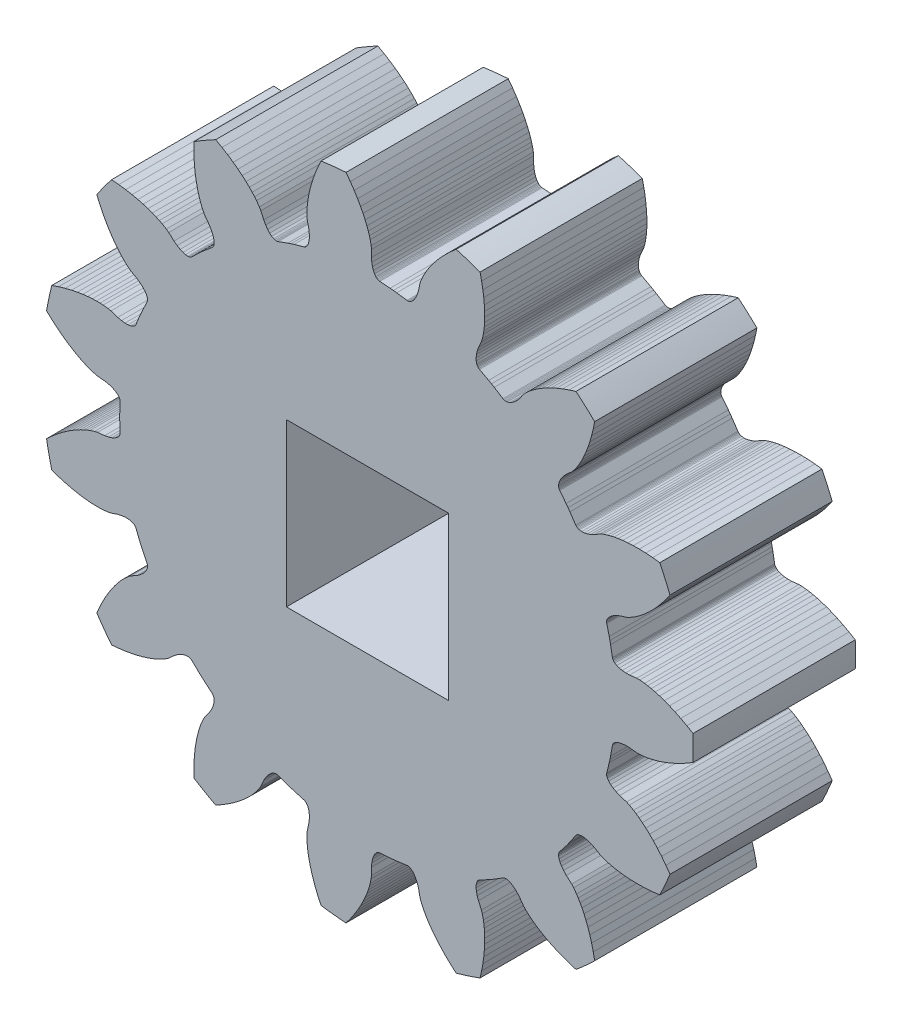
SolidWorks part; units mm, degrees
ref_plane "Front Plane" through (0, 0, 0) normal (0, 0, 1) x (1, 0, 0)
ref_plane "Top Plane" through (0, 0, 0) normal (0, 1, 0) x (1, 0, 0)
ref_plane "Right Plane" through (0, 0, 0) normal (1, 0, 0) x (0, 0, -1)
sketch "Model" plane through (0, 0, 0) normal (0, 0, 1) x (1, 0, 0)
  line L0 (11.6767, 4.5035) -> (11.5103, 4.2885)
  line L1 (11.5103, 4.2885) -> (11.3474, 4.0954)
  line L2 (11.3474, 4.0954) -> (11.1891, 3.9228)
  line L3 (11.1891, 3.9228) -> (11.0382, 3.7715)
  line L4 (11.0382, 3.7715) -> (10.8925, 3.6371)
  line L5 (10.8925, 3.6371) -> (10.7549, 3.5206)
  line L6 (10.7549, 3.5206) -> (10.6294, 3.4231)
  line L7 (10.6294, 3.4231) -> (10.5151, 3.3416)
  line L8 (10.5151, 3.3416) -> (10.4119, 3.2743)
  line L9 (10.4119, 3.2743) -> (10.2465, 3.1803)
  line L10 (10.2465, 3.1803) -> (10.1399, 3.1309)
  line L11 (10.1399, 3.1309) -> (9.873, 3.0467)
  line L12 (9.873, 3.0467) -> (9.7318, 2.9862)
  line L13 (9.7318, 2.9862) -> (9.613, 2.9201)
  line L14 (9.613, 2.9201) -> (9.5168, 2.8501)
  line L15 (9.5168, 2.8501) -> (9.4433, 2.778)
  line L16 (9.4433, 2.778) -> (9.3924, 2.7056)
  line L17 (9.3924, 2.7056) -> (9.3754, 2.6698)
  line L18 (9.3754, 2.6698) -> (9.364, 2.6346)
  line L19 (9.364, 2.6346) -> (9.3582, 2.6002)
  line L20 (9.3582, 2.6002) -> (9.3579, 2.5668)
  line L21 (9.3579, 2.5668) -> (9.363, 2.5346)
  line L22 (9.363, 2.5346) -> (9.4607, 2.1415)
  line L23 (9.4607, 2.1415) -> (9.488, 2.0167)
  line L24 (9.488, 2.0167) -> (9.5138, 1.8917)
  line L25 (9.5138, 1.8917) -> (9.5845, 1.4928)
  line L26 (9.5845, 1.4928) -> (9.5928, 1.4613)
  line L27 (9.5928, 1.4613) -> (9.6067, 1.4309)
  line L28 (9.6067, 1.4309) -> (9.626, 1.4019)
  line L29 (9.626, 1.4019) -> (9.6508, 1.3743)
  line L30 (9.6508, 1.3743) -> (9.6808, 1.3485)
  line L31 (9.6808, 1.3485) -> (9.7568, 1.3031)
  line L32 (9.7568, 1.3031) -> (9.8533, 1.2671)
  line L33 (9.8533, 1.2671) -> (9.9696, 1.2423)
  line L34 (9.9696, 1.2423) -> (10.105, 1.2303)
  line L35 (10.105, 1.2303) -> (10.2586, 1.2324)
  line L36 (10.2586, 1.2324) -> (10.5367, 1.2641)
  line L37 (10.5367, 1.2641) -> (10.6542, 1.2623)
  line L38 (10.6542, 1.2623) -> (10.8435, 1.2437)
  line L39 (10.8435, 1.2437) -> (10.9652, 1.2242)
  line L40 (10.9652, 1.2242) -> (11.1027, 1.1962)
  line L41 (11.1027, 1.1962) -> (11.2571, 1.1582)
  line L42 (11.2571, 1.1582) -> (11.4301, 1.1077)
  line L43 (11.4301, 1.1077) -> (11.6179, 1.0442)
  line L44 (11.6179, 1.0442) -> (11.8173, 0.9674)
  line L45 (11.8173, 0.9674) -> (12.0321, 0.8741)
  line L46 (12.0321, 0.8741) -> (12.2594, 0.764)
  line L47 (12.2594, 0.764) -> (12.499, 0.6352)
  line L48 (12.499, 0.6352) -> (12.7405, 0.492)
  line L49 (12.7405, -0.492) -> (12.499, -0.6352)
  line L50 (12.499, -0.6352) -> (12.2594, -0.764)
  line L51 (12.2594, -0.764) -> (12.0321, -0.8741)
  line L52 (12.0321, -0.8741) -> (11.8173, -0.9674)
  line L53 (11.8173, -0.9674) -> (11.6179, -1.0442)
  line L54 (11.6179, -1.0442) -> (11.4301, -1.1077)
  line L55 (11.4301, -1.1077) -> (11.2571, -1.1582)
  line L56 (11.2571, -1.1582) -> (11.1027, -1.1962)
  line L57 (11.1027, -1.1962) -> (10.9652, -1.2242)
  line L58 (10.9652, -1.2242) -> (10.8435, -1.2437)
  line L59 (10.8435, -1.2437) -> (10.6542, -1.2623)
  line L60 (10.6542, -1.2623) -> (10.5367, -1.2641)
  line L61 (10.5367, -1.2641) -> (10.2586, -1.2324)
  line L62 (10.2586, -1.2324) -> (10.105, -1.2303)
  line L63 (10.105, -1.2303) -> (9.9696, -1.2423)
  line L64 (9.9696, -1.2423) -> (9.8533, -1.2671)
  line L65 (9.8533, -1.2671) -> (9.7568, -1.3031)
  line L66 (9.7568, -1.3031) -> (9.6808, -1.3485)
  line L67 (9.6808, -1.3485) -> (9.6508, -1.3743)
  line L68 (9.6508, -1.3743) -> (9.626, -1.4019)
  line L69 (9.626, -1.4019) -> (9.6067, -1.4309)
  line L70 (9.6067, -1.4309) -> (9.5928, -1.4613)
  line L71 (9.5928, -1.4613) -> (9.5845, -1.4928)
  line L72 (9.5845, -1.4928) -> (9.5138, -1.8917)
  line L73 (9.5138, -1.8917) -> (9.488, -2.0167)
  line L74 (9.488, -2.0167) -> (9.4607, -2.1415)
  line L75 (9.4607, -2.1415) -> (9.363, -2.5346)
  line L76 (9.363, -2.5346) -> (9.3579, -2.5668)
  line L77 (9.3579, -2.5668) -> (9.3582, -2.6002)
  line L78 (9.3582, -2.6002) -> (9.364, -2.6346)
  line L79 (9.364, -2.6346) -> (9.3754, -2.6698)
  line L80 (9.3754, -2.6698) -> (9.3924, -2.7056)
  line L81 (9.3924, -2.7056) -> (9.4433, -2.778)
  line L82 (9.4433, -2.778) -> (9.5168, -2.8501)
  line L83 (9.5168, -2.8501) -> (9.613, -2.9201)
  line L84 (9.613, -2.9201) -> (9.7318, -2.9862)
  line L85 (9.7318, -2.9862) -> (9.873, -3.0467)
  line L86 (9.873, -3.0467) -> (10.1399, -3.1309)
  line L87 (10.1399, -3.1309) -> (10.2465, -3.1803)
  line L88 (10.2465, -3.1803) -> (10.4119, -3.2743)
  line L89 (10.4119, -3.2743) -> (10.5151, -3.3416)
  line L90 (10.5151, -3.3416) -> (10.6294, -3.4231)
  line L91 (10.6294, -3.4231) -> (10.7549, -3.5206)
  line L92 (10.7549, -3.5206) -> (10.8925, -3.6371)
  line L93 (10.8925, -3.6371) -> (11.0382, -3.7715)
  line L94 (11.0382, -3.7715) -> (11.1891, -3.9228)
  line L95 (11.1891, -3.9228) -> (11.3474, -4.0954)
  line L96 (11.3474, -4.0954) -> (11.5103, -4.2885)
  line L97 (11.5103, -4.2885) -> (11.6767, -4.5035)
  line L98 (11.6767, -4.5035) -> (11.8391, -4.7326)
  line L99 (11.4389, -5.6315) -> (11.16, -5.6641)
  line L100 (11.16, -5.6641) -> (10.8888, -5.6843)
  line L101 (10.8888, -5.6843) -> (10.6364, -5.6925)
  line L102 (10.6364, -5.6925) -> (10.4021, -5.6903)
  line L103 (10.4021, -5.6903) -> (10.1888, -5.6793)
  line L104 (10.1888, -5.6793) -> (9.9914, -5.661)
  line L105 (9.9914, -5.661) -> (9.8128, -5.6367)
  line L106 (9.8128, -5.6367) -> (9.6563, -5.6087)
  line L107 (9.6563, -5.6087) -> (9.5193, -5.5783)
  line L108 (9.5193, -5.5783) -> (9.4002, -5.5466)
  line L109 (9.4002, -5.5466) -> (9.2197, -5.4866)
  line L110 (9.2197, -5.4866) -> (9.1116, -5.4405)
  line L111 (9.1116, -5.4405) -> (8.8704, -5.2984)
  line L112 (8.8704, -5.2984) -> (8.731, -5.234)
  line L113 (8.731, -5.234) -> (8.6024, -5.1899)
  line L114 (8.6024, -5.1899) -> (8.486, -5.1653)
  line L115 (8.486, -5.1653) -> (8.3833, -5.1589)
  line L116 (8.3833, -5.1589) -> (8.2954, -5.1695)
  line L117 (8.2954, -5.1695) -> (8.2574, -5.1808)
  line L118 (8.2574, -5.1808) -> (8.2236, -5.1959)
  line L119 (8.2236, -5.1959) -> (8.1941, -5.2146)
  line L120 (8.1941, -5.2146) -> (8.1691, -5.2367)
  line L121 (8.1691, -5.2367) -> (8.1487, -5.2621)
  line L122 (8.1487, -5.2621) -> (7.9219, -5.5977)
  line L123 (7.9219, -5.5977) -> (7.8475, -5.7015)
  line L124 (7.8475, -5.7015) -> (7.7717, -5.8044)
  line L125 (7.7717, -5.8044) -> (7.5226, -6.1238)
  line L126 (7.5226, -6.1238) -> (7.5048, -6.151)
  line L127 (7.5048, -6.151) -> (7.4915, -6.1817)
  line L128 (7.4915, -6.1817) -> (7.4828, -6.2155)
  line L129 (7.4828, -6.2155) -> (7.4789, -6.2523)
  line L130 (7.4789, -6.2523) -> (7.4799, -6.2919)
  line L131 (7.4799, -6.2919) -> (7.4969, -6.3788)
  line L132 (7.4969, -6.3788) -> (7.5348, -6.4746)
  line L133 (7.5348, -6.4746) -> (7.5942, -6.5776)
  line L134 (7.5942, -6.5776) -> (7.6759, -6.6863)
  line L135 (7.6759, -6.6863) -> (7.7802, -6.799)
  line L136 (7.7802, -6.799) -> (7.9899, -6.9845)
  line L137 (7.9899, -6.9845) -> (8.0671, -7.073)
  line L138 (8.0671, -7.073) -> (8.1799, -7.2261)
  line L139 (8.1799, -7.2261) -> (8.2469, -7.3296)
  line L140 (8.2469, -7.3296) -> (8.3182, -7.4505)
  line L141 (8.3182, -7.4505) -> (8.3931, -7.5907)
  line L142 (8.3931, -7.5907) -> (8.4714, -7.753)
  line L143 (8.4714, -7.753) -> (8.5499, -7.9351)
  line L144 (8.5499, -7.9351) -> (8.6262, -8.1346)
  line L145 (8.6262, -8.1346) -> (8.7007, -8.3567)
  line L146 (8.7007, -8.3567) -> (8.7709, -8.5993)
  line L147 (8.7709, -8.5993) -> (8.8355, -8.8635)
  line L148 (8.8355, -8.8635) -> (8.8906, -9.1388)
  line L149 (8.1594, -9.7972) -> (7.8914, -9.7136)
  line L150 (7.8914, -9.7136) -> (7.6354, -9.6217)
  line L151 (7.6354, -9.6217) -> (7.4015, -9.5265)
  line L152 (7.4015, -9.5265) -> (7.1884, -9.4292)
  line L153 (7.1884, -9.4292) -> (6.9979, -9.3325)
  line L154 (6.9979, -9.3325) -> (6.8251, -9.2354)
  line L155 (6.8251, -9.2354) -> (6.6718, -9.1406)
  line L156 (6.6718, -9.1406) -> (6.5402, -9.0514)
  line L157 (6.5402, -9.0514) -> (6.4274, -8.9679)
  line L158 (6.4274, -8.9679) -> (6.3315, -8.8905)
  line L159 (6.3315, -8.8905) -> (6.191, -8.7623)
  line L160 (6.191, -8.7623) -> (6.111, -8.6762)
  line L161 (6.111, -8.6762) -> (5.9485, -8.4483)
  line L162 (5.9485, -8.4483) -> (5.8473, -8.3327)
  line L163 (5.8473, -8.3327) -> (5.7478, -8.2402)
  line L164 (5.7478, -8.2402) -> (5.6515, -8.1703)
  line L165 (5.6515, -8.1703) -> (5.5602, -8.1226)
  line L166 (5.5602, -8.1226) -> (5.4756, -8.0966)
  line L167 (5.4756, -8.0966) -> (5.4363, -8.0915)
  line L168 (5.4363, -8.0915) -> (5.3993, -8.0916)
  line L169 (5.3993, -8.0916) -> (5.3647, -8.0966)
  line L170 (5.3647, -8.0966) -> (5.3329, -8.1067)
  line L171 (5.3329, -8.1067) -> (5.3039, -8.1215)
  line L172 (5.3039, -8.1215) -> (4.9602, -8.3359)
  line L173 (4.9602, -8.3359) -> (4.85, -8.4004)
  line L174 (4.85, -8.4004) -> (4.739, -8.4636)
  line L175 (4.739, -8.4636) -> (4.3815, -8.6541)
  line L176 (4.3815, -8.6541) -> (4.3542, -8.6717)
  line L177 (4.3542, -8.6717) -> (4.3295, -8.6943)
  line L178 (4.3295, -8.6943) -> (4.3078, -8.7217)
  line L179 (4.3078, -8.7217) -> (4.2893, -8.7537)
  line L180 (4.2893, -8.7537) -> (4.2741, -8.7903)
  line L181 (4.2741, -8.7903) -> (4.2543, -8.8766)
  line L182 (4.2543, -8.8766) -> (4.2499, -8.9795)
  line L183 (4.2499, -8.9795) -> (4.2623, -9.0978)
  line L184 (4.2623, -9.0978) -> (4.2927, -9.2303)
  line L185 (4.2927, -9.2303) -> (4.3422, -9.3757)
  line L186 (4.3422, -9.3757) -> (4.4583, -9.6304)
  line L187 (4.4583, -9.6304) -> (4.4928, -9.7427)
  line L188 (4.4928, -9.7427) -> (4.5336, -9.9285)
  line L189 (4.5336, -9.9285) -> (4.5527, -10.0502)
  line L190 (4.5527, -10.0502) -> (4.5686, -10.1897)
  line L191 (4.5686, -10.1897) -> (4.5801, -10.3482)
  line L192 (4.5801, -10.3482) -> (4.5856, -10.5284)
  line L193 (4.5856, -10.5284) -> (4.5832, -10.7266)
  line L194 (4.5832, -10.7266) -> (4.5718, -10.94)
  line L195 (4.5718, -10.94) -> (4.5495, -11.1731)
  line L196 (4.5495, -11.1731) -> (4.5149, -11.4233)
  line L197 (4.5149, -11.4233) -> (4.4665, -11.691)
  line L198 (4.4665, -11.691) -> (4.4049, -11.9649)
  line L199 (3.4691, -12.2689) -> (3.2583, -12.0835)
  line L200 (3.2583, -12.0835) -> (3.0618, -11.8955)
  line L201 (3.0618, -11.8955) -> (2.8868, -11.7134)
  line L202 (2.8868, -11.7134) -> (2.7317, -11.5378)
  line L203 (2.7317, -11.5378) -> (2.597, -11.3719)
  line L204 (2.597, -11.3719) -> (2.4786, -11.213)
  line L205 (2.4786, -11.213) -> (2.3771, -11.064)
  line L206 (2.3771, -11.064) -> (2.2932, -10.929)
  line L207 (2.2932, -10.929) -> (2.2242, -10.8068)
  line L208 (2.2242, -10.8068) -> (2.168, -10.6971)
  line L209 (2.168, -10.6971) -> (2.0918, -10.5228)
  line L210 (2.0918, -10.5228) -> (2.0538, -10.4117)
  line L211 (2.0538, -10.4117) -> (1.998, -10.1374)
  line L212 (1.998, -10.1374) -> (1.9526, -9.9906)
  line L213 (1.9526, -9.9906) -> (1.8993, -9.8656)
  line L214 (1.8993, -9.8656) -> (1.8397, -9.7626)
  line L215 (1.8397, -9.7626) -> (1.7757, -9.6819)
  line L216 (1.7757, -9.6819) -> (1.709, -9.6238)
  line L217 (1.709, -9.6238) -> (1.6752, -9.6031)
  line L218 (1.6752, -9.6031) -> (1.6414, -9.5881)
  line L219 (1.6414, -9.5881) -> (1.6077, -9.5787)
  line L220 (1.6077, -9.5787) -> (1.5745, -9.5749)
  line L221 (1.5745, -9.5749) -> (1.542, -9.5767)
  line L222 (1.542, -9.5767) -> (1.1409, -9.6327)
  line L223 (1.1409, -9.6327) -> (1.0139, -9.6469)
  line L224 (1.0139, -9.6469) -> (0.8868, -9.6594)
  line L225 (0.8868, -9.6594) -> (0.4828, -9.688)
  line L226 (0.4828, -9.688) -> (0.4506, -9.693)
  line L227 (0.4506, -9.693) -> (0.4189, -9.7036)
  line L228 (0.4189, -9.7036) -> (0.388, -9.7198)
  line L229 (0.388, -9.7198) -> (0.358, -9.7415)
  line L230 (0.358, -9.7415) -> (0.3292, -9.7688)
  line L231 (0.3292, -9.7688) -> (0.2761, -9.8396)
  line L232 (0.2761, -9.8396) -> (0.2302, -9.9318)
  line L233 (0.2302, -9.9318) -> (0.1934, -10.0449)
  line L234 (0.1934, -10.0449) -> (0.1672, -10.1783)
  line L235 (0.1672, -10.1783) -> (0.1534, -10.3312)
  line L236 (0.1534, -10.3312) -> (0.1558, -10.6111)
  line L237 (0.1558, -10.6111) -> (0.1417, -10.7278)
  line L238 (0.1417, -10.7278) -> (0.1034, -10.9141)
  line L239 (0.1034, -10.9141) -> (0.0713, -11.0331)
  line L240 (0.0713, -11.0331) -> (0.0291, -11.1669)
  line L241 (0.0291, -11.1669) -> (-0.0249, -11.3165)
  line L242 (-0.0249, -11.3165) -> (-0.0932, -11.4833)
  line L243 (-0.0932, -11.4833) -> (-0.1759, -11.6634)
  line L244 (-0.1759, -11.6634) -> (-0.2732, -11.8536)
  line L245 (-0.2732, -11.8536) -> (-0.3884, -12.0576)
  line L246 (-0.3884, -12.0576) -> (-0.5217, -12.2721)
  line L247 (-0.5217, -12.2721) -> (-0.6748, -12.4969)
  line L248 (-0.6748, -12.4969) -> (-0.8425, -12.7221)
  line L249 (-1.821, -12.6193) -> (-1.9382, -12.3641)
  line L250 (-1.9382, -12.3641) -> (-2.0412, -12.1124)
  line L251 (-2.0412, -12.1124) -> (-2.127, -11.8749)
  line L252 (-2.127, -11.8749) -> (-2.1973, -11.6514)
  line L253 (-2.1973, -11.6514) -> (-2.2529, -11.4451)
  line L254 (-2.2529, -11.4451) -> (-2.2964, -11.2517)
  line L255 (-2.2964, -11.2517) -> (-2.3285, -11.0743)
  line L256 (-2.3285, -11.0743) -> (-2.3502, -10.9169)
  line L257 (-2.3502, -10.9169) -> (-2.3637, -10.7771)
  line L258 (-2.3637, -10.7771) -> (-2.3703, -10.6541)
  line L259 (-2.3703, -10.6541) -> (-2.369, -10.4639)
  line L260 (-2.369, -10.4639) -> (-2.3586, -10.3469)
  line L261 (-2.3586, -10.3469) -> (-2.298, -10.0736)
  line L262 (-2.298, -10.0736) -> (-2.2798, -9.9211)
  line L263 (-2.2798, -9.9211) -> (-2.2776, -9.7852)
  line L264 (-2.2776, -9.7852) -> (-2.2901, -9.6669)
  line L265 (-2.2901, -9.6669) -> (-2.3158, -9.5671)
  line L266 (-2.3158, -9.5671) -> (-2.3531, -9.4868)
  line L267 (-2.3531, -9.4868) -> (-2.3756, -9.4542)
  line L268 (-2.3756, -9.4542) -> (-2.4004, -9.4268)
  line L269 (-2.4004, -9.4268) -> (-2.4273, -9.4045)
  line L270 (-2.4273, -9.4045) -> (-2.456, -9.3875)
  line L271 (-2.456, -9.3875) -> (-2.4865, -9.3759)
  line L272 (-2.4865, -9.3759) -> (-2.8758, -9.2639)
  line L273 (-2.8758, -9.2639) -> (-2.9975, -9.2252)
  line L274 (-2.9975, -9.2252) -> (-3.1187, -9.185)
  line L275 (-3.1187, -9.185) -> (-3.4994, -9.0468)
  line L276 (-3.4994, -9.0468) -> (-3.5309, -9.0383)
  line L277 (-3.5309, -9.0383) -> (-3.5641, -9.0351)
  line L278 (-3.5641, -9.0351) -> (-3.599, -9.0373)
  line L279 (-3.599, -9.0373) -> (-3.6352, -9.045)
  line L280 (-3.6352, -9.045) -> (-3.6725, -9.0581)
  line L281 (-3.6725, -9.0581) -> (-3.7499, -9.1012)
  line L282 (-3.7499, -9.1012) -> (-3.8293, -9.1668)
  line L283 (-3.8293, -9.1668) -> (-3.9089, -9.2551)
  line L284 (-3.9089, -9.2551) -> (-3.9871, -9.3664)
  line L285 (-3.9871, -9.3664) -> (-4.062, -9.5004)
  line L286 (-4.062, -9.5004) -> (-4.1736, -9.7571)
  line L287 (-4.1736, -9.7571) -> (-4.234, -9.858)
  line L288 (-4.234, -9.858) -> (-4.3447, -10.0126)
  line L289 (-4.3447, -10.0126) -> (-4.4224, -10.1082)
  line L290 (-4.4224, -10.1082) -> (-4.5154, -10.2134)
  line L291 (-4.5154, -10.2134) -> (-4.6255, -10.328)
  line L292 (-4.6255, -10.328) -> (-4.7558, -10.4526)
  line L293 (-4.7558, -10.4526) -> (-4.9046, -10.5835)
  line L294 (-4.9046, -10.5835) -> (-5.0709, -10.7177)
  line L295 (-5.0709, -10.7177) -> (-5.2591, -10.8572)
  line L296 (-5.2591, -10.8572) -> (-5.4681, -10.999)
  line L297 (-5.4681, -10.999) -> (-5.6994, -11.142)
  line L298 (-5.6994, -11.142) -> (-5.9442, -11.2796)
  line L299 (-6.7963, -10.7876) -> (-6.7996, -10.5068)
  line L300 (-6.7996, -10.5068) -> (-6.7913, -10.235)
  line L301 (-6.7913, -10.235) -> (-6.7731, -9.9831)
  line L302 (-6.7731, -9.9831) -> (-6.7464, -9.7504)
  line L303 (-6.7464, -9.7504) -> (-6.7132, -9.5393)
  line L304 (-6.7132, -9.5393) -> (-6.6743, -9.3449)
  line L305 (-6.6743, -9.3449) -> (-6.6315, -9.1698)
  line L306 (-6.6315, -9.1698) -> (-6.5873, -9.0171)
  line L307 (-6.5873, -9.0171) -> (-6.5428, -8.884)
  line L308 (-6.5428, -8.884) -> (-6.4988, -8.7689)
  line L309 (-6.4988, -8.7689) -> (-6.4203, -8.5957)
  line L310 (-6.4203, -8.5957) -> (-6.3631, -8.493)
  line L311 (-6.3631, -8.493) -> (-6.1966, -8.268)
  line L312 (-6.1966, -8.268) -> (-6.118, -8.1361)
  line L313 (-6.118, -8.1361) -> (-6.0607, -8.0128)
  line L314 (-6.0607, -8.0128) -> (-6.024, -7.8996)
  line L315 (-6.024, -7.8996) -> (-6.0069, -7.7981)
  line L316 (-6.0069, -7.7981) -> (-6.0083, -7.7096)
  line L317 (-6.0083, -7.7096) -> (-6.0156, -7.6706)
  line L318 (-6.0156, -7.6706) -> (-6.0271, -7.6354)
  line L319 (-6.0271, -7.6354) -> (-6.0426, -7.6042)
  line L320 (-6.0426, -7.6042) -> (-6.062, -7.577)
  line L321 (-6.062, -7.577) -> (-6.0851, -7.554)
  line L322 (-6.0851, -7.554) -> (-6.3951, -7.2934)
  line L323 (-6.3951, -7.2934) -> (-6.4906, -7.2085)
  line L324 (-6.4906, -7.2085) -> (-6.5849, -7.1224)
  line L325 (-6.5849, -7.1224) -> (-6.8765, -6.8413)
  line L326 (-6.8765, -6.8413) -> (-6.9018, -6.8208)
  line L327 (-6.9018, -6.8208) -> (-6.9309, -6.8043)
  line L328 (-6.9309, -6.8043) -> (-6.9636, -6.7922)
  line L329 (-6.9636, -6.7922) -> (-6.9998, -6.7844)
  line L330 (-6.9998, -6.7844) -> (-7.0393, -6.7813)
  line L331 (-7.0393, -6.7813) -> (-7.1275, -6.7891)
  line L332 (-7.1275, -6.7891) -> (-7.2267, -6.8167)
  line L333 (-7.2267, -6.8167) -> (-7.3354, -6.8651)
  line L334 (-7.3354, -6.8651) -> (-7.452, -6.9349)
  line L335 (-7.452, -6.9349) -> (-7.575, -7.0269)
  line L336 (-7.575, -7.0269) -> (-7.7814, -7.216)
  line L337 (-7.7814, -7.216) -> (-7.8775, -7.2836)
  line L338 (-7.8775, -7.2836) -> (-8.0416, -7.3798)
  line L339 (-8.0416, -7.3798) -> (-8.1515, -7.4356)
  line L340 (-8.1515, -7.4356) -> (-8.2792, -7.4938)
  line L341 (-8.2792, -7.4938) -> (-8.4264, -7.5537)
  line L342 (-8.4264, -7.5537) -> (-8.5961, -7.6146)
  line L343 (-8.5961, -7.6146) -> (-8.7853, -7.6736)
  line L344 (-8.7853, -7.6736) -> (-8.9918, -7.7286)
  line L345 (-8.9918, -7.7286) -> (-9.2204, -7.7795)
  line L346 (-9.2204, -7.7795) -> (-9.469, -7.824)
  line L347 (-9.469, -7.824) -> (-9.7385, -7.8606)
  line L348 (-9.7385, -7.8606) -> (-10.0181, -7.8867)
  line L349 (-10.5964, -7.0906) -> (-10.4852, -6.8328)
  line L350 (-10.4852, -6.8328) -> (-10.3671, -6.5879)
  line L351 (-10.3671, -6.5879) -> (-10.248, -6.3651)
  line L352 (-10.248, -6.3651) -> (-10.129, -6.1634)
  line L353 (-10.129, -6.1634) -> (-10.0128, -5.984)
  line L354 (-10.0128, -5.984) -> (-9.8982, -5.8223)
  line L355 (-9.8982, -5.8223) -> (-9.7879, -5.6798)
  line L356 (-9.7879, -5.6798) -> (-9.6854, -5.5582)
  line L357 (-9.6854, -5.5582) -> (-9.5906, -5.4548)
  line L358 (-9.5906, -5.4548) -> (-9.5036, -5.3675)
  line L359 (-9.5036, -5.3675) -> (-9.3614, -5.2412)
  line L360 (-9.3614, -5.2412) -> (-9.2674, -5.1707)
  line L361 (-9.2674, -5.1707) -> (-9.0238, -5.0328)
  line L362 (-9.0238, -5.0328) -> (-8.8983, -4.9443)
  line L363 (-8.8983, -4.9443) -> (-8.7958, -4.855)
  line L364 (-8.7958, -4.855) -> (-8.7163, -4.7665)
  line L365 (-8.7163, -4.7665) -> (-8.6593, -4.6807)
  line L366 (-8.6593, -4.6807) -> (-8.6246, -4.5993)
  line L367 (-8.6246, -4.5993) -> (-8.6154, -4.5607)
  line L368 (-8.6154, -4.5607) -> (-8.6116, -4.5239)
  line L369 (-8.6116, -4.5239) -> (-8.6131, -4.489)
  line L370 (-8.6131, -4.489) -> (-8.6197, -4.4563)
  line L371 (-8.6197, -4.4563) -> (-8.6315, -4.4259)
  line L372 (-8.6315, -4.4259) -> (-8.8087, -4.0617)
  line L373 (-8.8087, -4.0617) -> (-8.8614, -3.9453)
  line L374 (-8.8614, -3.9453) -> (-8.9126, -3.8283)
  line L375 (-8.9126, -3.8283) -> (-9.0646, -3.4529)
  line L376 (-9.0646, -3.4529) -> (-9.0794, -3.4239)
  line L377 (-9.0794, -3.4239) -> (-9.0993, -3.397)
  line L378 (-9.0993, -3.397) -> (-9.1242, -3.3726)
  line L379 (-9.1242, -3.3726) -> (-9.1541, -3.3508)
  line L380 (-9.1541, -3.3508) -> (-9.1889, -3.3318)
  line L381 (-9.1889, -3.3318) -> (-9.2727, -3.3032)
  line L382 (-9.2727, -3.3032) -> (-9.3745, -3.2881)
  line L383 (-9.3745, -3.2881) -> (-9.4935, -3.288)
  line L384 (-9.4935, -3.288) -> (-9.6284, -3.3043)
  line L385 (-9.6284, -3.3043) -> (-9.7782, -3.3384)
  line L386 (-9.7782, -3.3384) -> (-10.0437, -3.4272)
  line L387 (-10.0437, -3.4272) -> (-10.159, -3.4498)
  line L388 (-10.159, -3.4498) -> (-10.348, -3.471)
  line L389 (-10.348, -3.471) -> (-10.471, -3.4772)
  line L390 (-10.471, -3.4772) -> (-10.6114, -3.4785)
  line L391 (-10.6114, -3.4785) -> (-10.7703, -3.4733)
  line L392 (-10.7703, -3.4733) -> (-10.95, -3.4599)
  line L393 (-10.95, -3.4599) -> (-11.1469, -3.4369)
  line L394 (-11.1469, -3.4369) -> (-11.3579, -3.4032)
  line L395 (-11.3579, -3.4032) -> (-11.5875, -3.3566)
  line L396 (-11.5875, -3.3566) -> (-11.8327, -3.2961)
  line L397 (-11.8327, -3.2961) -> (-12.0938, -3.22)
  line L398 (-12.0938, -3.22) -> (-12.3598, -3.1301)
  line L399 (-12.5643, -2.1677) -> (-12.3579, -1.9774)
  line L400 (-12.3579, -1.9774) -> (-12.1504, -1.8016)
  line L401 (-12.1504, -1.8016) -> (-11.951, -1.6466)
  line L402 (-11.951, -1.6466) -> (-11.7602, -1.5107)
  line L403 (-11.7602, -1.5107) -> (-11.5811, -1.3941)
  line L404 (-11.5811, -1.3941) -> (-11.4106, -1.293)
  line L405 (-11.4106, -1.293) -> (-11.2519, -1.2076)
  line L406 (-11.2519, -1.2076) -> (-11.1088, -1.1383)
  line L407 (-11.1088, -1.1383) -> (-10.9801, -1.0823)
  line L408 (-10.9801, -1.0823) -> (-10.8651, -1.038)
  line L409 (-10.8651, -1.038) -> (-10.6838, -0.9805)
  line L410 (-10.6838, -0.9805) -> (-10.5693, -0.9542)
  line L411 (-10.5693, -0.9542) -> (-10.2907, -0.9274)
  line L412 (-10.2907, -0.9274) -> (-10.14, -0.8976)
  line L413 (-10.14, -0.8976) -> (-10.0101, -0.8576)
  line L414 (-10.0101, -0.8576) -> (-9.9014, -0.8092)
  line L415 (-9.9014, -0.8092) -> (-9.8145, -0.754)
  line L416 (-9.8145, -0.754) -> (-9.7497, -0.6937)
  line L417 (-9.7497, -0.6937) -> (-9.7256, -0.6622)
  line L418 (-9.7256, -0.6622) -> (-9.7071, -0.6301)
  line L419 (-9.7071, -0.6301) -> (-9.6943, -0.5977)
  line L420 (-9.6943, -0.5977) -> (-9.687, -0.5651)
  line L421 (-9.687, -0.5651) -> (-9.6854, -0.5325)
  line L422 (-9.6854, -0.5325) -> (-9.6992, -0.1277)
  line L423 (-9.6992, -0.1277) -> (-9.7, 0)
  line L424 (-9.7, 0) -> (-9.6992, 0.1277)
  line L425 (-9.6992, 0.1277) -> (-9.6854, 0.5325)
  line L426 (-9.6854, 0.5325) -> (-9.687, 0.5651)
  line L427 (-9.687, 0.5651) -> (-9.6943, 0.5977)
  line L428 (-9.6943, 0.5977) -> (-9.7071, 0.6301)
  line L429 (-9.7071, 0.6301) -> (-9.7256, 0.6622)
  line L430 (-9.7256, 0.6622) -> (-9.7497, 0.6937)
  line L431 (-9.7497, 0.6937) -> (-9.8145, 0.754)
  line L432 (-9.8145, 0.754) -> (-9.9014, 0.8092)
  line L433 (-9.9014, 0.8092) -> (-10.0101, 0.8576)
  line L434 (-10.0101, 0.8576) -> (-10.14, 0.8976)
  line L435 (-10.14, 0.8976) -> (-10.2907, 0.9274)
  line L436 (-10.2907, 0.9274) -> (-10.5693, 0.9542)
  line L437 (-10.5693, 0.9542) -> (-10.6838, 0.9805)
  line L438 (-10.6838, 0.9805) -> (-10.8651, 1.038)
  line L439 (-10.8651, 1.038) -> (-10.9801, 1.0823)
  line L440 (-10.9801, 1.0823) -> (-11.1088, 1.1383)
  line L441 (-11.1088, 1.1383) -> (-11.2519, 1.2076)
  line L442 (-11.2519, 1.2076) -> (-11.4106, 1.293)
  line L443 (-11.4106, 1.293) -> (-11.5811, 1.3941)
  line L444 (-11.5811, 1.3941) -> (-11.7602, 1.5107)
  line L445 (-11.7602, 1.5107) -> (-11.951, 1.6466)
  line L446 (-11.951, 1.6466) -> (-12.1504, 1.8016)
  line L447 (-12.1504, 1.8016) -> (-12.3579, 1.9774)
  line L448 (-12.3579, 1.9774) -> (-12.5643, 2.1677)
  line L449 (-12.3598, 3.1301) -> (-12.0938, 3.22)
  line L450 (-12.0938, 3.22) -> (-11.8327, 3.2961)
  line L451 (-11.8327, 3.2961) -> (-11.5875, 3.3566)
  line L452 (-11.5875, 3.3566) -> (-11.3579, 3.4032)
  line L453 (-11.3579, 3.4032) -> (-11.1469, 3.4369)
  line L454 (-11.1469, 3.4369) -> (-10.95, 3.4599)
  line L455 (-10.95, 3.4599) -> (-10.7703, 3.4733)
  line L456 (-10.7703, 3.4733) -> (-10.6114, 3.4785)
  line L457 (-10.6114, 3.4785) -> (-10.471, 3.4772)
  line L458 (-10.471, 3.4772) -> (-10.348, 3.471)
  line L459 (-10.348, 3.471) -> (-10.159, 3.4498)
  line L460 (-10.159, 3.4498) -> (-10.0437, 3.4272)
  line L461 (-10.0437, 3.4272) -> (-9.7782, 3.3384)
  line L462 (-9.7782, 3.3384) -> (-9.6284, 3.3043)
  line L463 (-9.6284, 3.3043) -> (-9.4935, 3.288)
  line L464 (-9.4935, 3.288) -> (-9.3745, 3.2881)
  line L465 (-9.3745, 3.2881) -> (-9.2727, 3.3032)
  line L466 (-9.2727, 3.3032) -> (-9.1889, 3.3318)
  line L467 (-9.1889, 3.3318) -> (-9.1541, 3.3508)
  line L468 (-9.1541, 3.3508) -> (-9.1242, 3.3726)
  line L469 (-9.1242, 3.3726) -> (-9.0993, 3.397)
  line L470 (-9.0993, 3.397) -> (-9.0794, 3.4239)
  line L471 (-9.0794, 3.4239) -> (-9.0646, 3.4529)
  line L472 (-9.0646, 3.4529) -> (-8.9126, 3.8283)
  line L473 (-8.9126, 3.8283) -> (-8.8614, 3.9453)
  line L474 (-8.8614, 3.9453) -> (-8.8087, 4.0617)
  line L475 (-8.8087, 4.0617) -> (-8.6315, 4.4259)
  line L476 (-8.6315, 4.4259) -> (-8.6197, 4.4563)
  line L477 (-8.6197, 4.4563) -> (-8.6131, 4.489)
  line L478 (-8.6131, 4.489) -> (-8.6116, 4.5239)
  line L479 (-8.6116, 4.5239) -> (-8.6154, 4.5607)
  line L480 (-8.6154, 4.5607) -> (-8.6246, 4.5993)
  line L481 (-8.6246, 4.5993) -> (-8.6593, 4.6807)
  line L482 (-8.6593, 4.6807) -> (-8.7163, 4.7665)
  line L483 (-8.7163, 4.7665) -> (-8.7958, 4.855)
  line L484 (-8.7958, 4.855) -> (-8.8983, 4.9443)
  line L485 (-8.8983, 4.9443) -> (-9.0238, 5.0328)
  line L486 (-9.0238, 5.0328) -> (-9.2674, 5.1707)
  line L487 (-9.2674, 5.1707) -> (-9.3614, 5.2412)
  line L488 (-9.3614, 5.2412) -> (-9.5036, 5.3675)
  line L489 (-9.5036, 5.3675) -> (-9.5906, 5.4548)
  line L490 (-9.5906, 5.4548) -> (-9.6854, 5.5582)
  line L491 (-9.6854, 5.5582) -> (-9.7879, 5.6798)
  line L492 (-9.7879, 5.6798) -> (-9.8982, 5.8223)
  line L493 (-9.8982, 5.8223) -> (-10.0128, 5.984)
  line L494 (-10.0128, 5.984) -> (-10.129, 6.1634)
  line L495 (-10.129, 6.1634) -> (-10.248, 6.3651)
  line L496 (-10.248, 6.3651) -> (-10.3671, 6.5879)
  line L497 (-10.3671, 6.5879) -> (-10.4852, 6.8328)
  line L498 (-10.4852, 6.8328) -> (-10.5964, 7.0906)
  line L499 (-10.0181, 7.8867) -> (-9.7385, 7.8606)
  line L500 (-9.7385, 7.8606) -> (-9.469, 7.824)
  line L501 (-9.469, 7.824) -> (-9.2204, 7.7795)
  line L502 (-9.2204, 7.7795) -> (-8.9918, 7.7286)
  line L503 (-8.9918, 7.7286) -> (-8.7853, 7.6736)
  line L504 (-8.7853, 7.6736) -> (-8.5961, 7.6146)
  line L505 (-8.5961, 7.6146) -> (-8.4264, 7.5537)
  line L506 (-8.4264, 7.5537) -> (-8.2792, 7.4938)
  line L507 (-8.2792, 7.4938) -> (-8.1515, 7.4356)
  line L508 (-8.1515, 7.4356) -> (-8.0416, 7.3798)
  line L509 (-8.0416, 7.3798) -> (-7.8775, 7.2836)
  line L510 (-7.8775, 7.2836) -> (-7.7814, 7.216)
  line L511 (-7.7814, 7.216) -> (-7.575, 7.0269)
  line L512 (-7.575, 7.0269) -> (-7.452, 6.9349)
  line L513 (-7.452, 6.9349) -> (-7.3354, 6.8651)
  line L514 (-7.3354, 6.8651) -> (-7.2267, 6.8167)
  line L515 (-7.2267, 6.8167) -> (-7.1275, 6.7891)
  line L516 (-7.1275, 6.7891) -> (-7.0393, 6.7813)
  line L517 (-7.0393, 6.7813) -> (-6.9998, 6.7844)
  line L518 (-6.9998, 6.7844) -> (-6.9636, 6.7922)
  line L519 (-6.9636, 6.7922) -> (-6.9309, 6.8043)
  line L520 (-6.9309, 6.8043) -> (-6.9018, 6.8208)
  line L521 (-6.9018, 6.8208) -> (-6.8765, 6.8413)
  line L522 (-6.8765, 6.8413) -> (-6.5849, 7.1224)
  line L523 (-6.5849, 7.1224) -> (-6.4906, 7.2085)
  line L524 (-6.4906, 7.2085) -> (-6.3951, 7.2934)
  line L525 (-6.3951, 7.2934) -> (-6.0851, 7.554)
  line L526 (-6.0851, 7.554) -> (-6.062, 7.577)
  line L527 (-6.062, 7.577) -> (-6.0426, 7.6042)
  line L528 (-6.0426, 7.6042) -> (-6.0271, 7.6354)
  line L529 (-6.0271, 7.6354) -> (-6.0156, 7.6706)
  line L530 (-6.0156, 7.6706) -> (-6.0083, 7.7096)
  line L531 (-6.0083, 7.7096) -> (-6.0069, 7.7981)
  line L532 (-6.0069, 7.7981) -> (-6.024, 7.8996)
  line L533 (-6.024, 7.8996) -> (-6.0607, 8.0128)
  line L534 (-6.0607, 8.0128) -> (-6.118, 8.1361)
  line L535 (-6.118, 8.1361) -> (-6.1966, 8.268)
  line L536 (-6.1966, 8.268) -> (-6.3631, 8.493)
  line L537 (-6.3631, 8.493) -> (-6.4203, 8.5957)
  line L538 (-6.4203, 8.5957) -> (-6.4988, 8.7689)
  line L539 (-6.4988, 8.7689) -> (-6.5428, 8.884)
  line L540 (-6.5428, 8.884) -> (-6.5873, 9.0171)
  line L541 (-6.5873, 9.0171) -> (-6.6315, 9.1698)
  line L542 (-6.6315, 9.1698) -> (-6.6743, 9.3449)
  line L543 (-6.6743, 9.3449) -> (-6.7132, 9.5393)
  line L544 (-6.7132, 9.5393) -> (-6.7464, 9.7504)
  line L545 (-6.7464, 9.7504) -> (-6.7731, 9.9831)
  line L546 (-6.7731, 9.9831) -> (-6.7913, 10.235)
  line L547 (-6.7913, 10.235) -> (-6.7996, 10.5068)
  line L548 (-6.7996, 10.5068) -> (-6.7963, 10.7876)
  line L549 (-5.9442, 11.2796) -> (-5.6994, 11.142)
  line L550 (-5.6994, 11.142) -> (-5.4681, 10.999)
  line L551 (-5.4681, 10.999) -> (-5.2591, 10.8572)
  line L552 (-5.2591, 10.8572) -> (-5.0709, 10.7177)
  line L553 (-5.0709, 10.7177) -> (-4.9046, 10.5835)
  line L554 (-4.9046, 10.5835) -> (-4.7558, 10.4526)
  line L555 (-4.7558, 10.4526) -> (-4.6255, 10.328)
  line L556 (-4.6255, 10.328) -> (-4.5154, 10.2134)
  line L557 (-4.5154, 10.2134) -> (-4.4224, 10.1082)
  line L558 (-4.4224, 10.1082) -> (-4.3447, 10.0126)
  line L559 (-4.3447, 10.0126) -> (-4.234, 9.858)
  line L560 (-4.234, 9.858) -> (-4.1736, 9.7571)
  line L561 (-4.1736, 9.7571) -> (-4.062, 9.5004)
  line L562 (-4.062, 9.5004) -> (-3.9871, 9.3664)
  line L563 (-3.9871, 9.3664) -> (-3.9089, 9.2551)
  line L564 (-3.9089, 9.2551) -> (-3.8293, 9.1668)
  line L565 (-3.8293, 9.1668) -> (-3.7499, 9.1012)
  line L566 (-3.7499, 9.1012) -> (-3.6725, 9.0581)
  line L567 (-3.6725, 9.0581) -> (-3.6352, 9.045)
  line L568 (-3.6352, 9.045) -> (-3.599, 9.0373)
  line L569 (-3.599, 9.0373) -> (-3.5641, 9.0351)
  line L570 (-3.5641, 9.0351) -> (-3.5309, 9.0383)
  line L571 (-3.5309, 9.0383) -> (-3.4994, 9.0468)
  line L572 (-3.4994, 9.0468) -> (-3.1187, 9.185)
  line L573 (-3.1187, 9.185) -> (-2.9975, 9.2252)
  line L574 (-2.9975, 9.2252) -> (-2.8758, 9.2639)
  line L575 (-2.8758, 9.2639) -> (-2.4865, 9.3759)
  line L576 (-2.4865, 9.3759) -> (-2.456, 9.3875)
  line L577 (-2.456, 9.3875) -> (-2.4273, 9.4045)
  line L578 (-2.4273, 9.4045) -> (-2.4004, 9.4268)
  line L579 (-2.4004, 9.4268) -> (-2.3756, 9.4542)
  line L580 (-2.3756, 9.4542) -> (-2.3531, 9.4868)
  line L581 (-2.3531, 9.4868) -> (-2.3158, 9.5671)
  line L582 (-2.3158, 9.5671) -> (-2.2901, 9.6669)
  line L583 (-2.2901, 9.6669) -> (-2.2776, 9.7852)
  line L584 (-2.2776, 9.7852) -> (-2.2798, 9.9211)
  line L585 (-2.2798, 9.9211) -> (-2.298, 10.0736)
  line L586 (-2.298, 10.0736) -> (-2.3586, 10.3469)
  line L587 (-2.3586, 10.3469) -> (-2.369, 10.4639)
  line L588 (-2.369, 10.4639) -> (-2.3703, 10.6541)
  line L589 (-2.3703, 10.6541) -> (-2.3637, 10.7771)
  line L590 (-2.3637, 10.7771) -> (-2.3502, 10.9169)
  line L591 (-2.3502, 10.9169) -> (-2.3285, 11.0743)
  line L592 (-2.3285, 11.0743) -> (-2.2964, 11.2517)
  line L593 (-2.2964, 11.2517) -> (-2.2529, 11.4451)
  line L594 (-2.2529, 11.4451) -> (-2.1973, 11.6514)
  line L595 (-2.1973, 11.6514) -> (-2.127, 11.8749)
  line L596 (-2.127, 11.8749) -> (-2.0412, 12.1124)
  line L597 (-2.0412, 12.1124) -> (-1.9382, 12.3641)
  line L598 (-1.9382, 12.3641) -> (-1.821, 12.6193)
  line L599 (-0.8425, 12.7221) -> (-0.6748, 12.4969)
  line L600 (-0.6748, 12.4969) -> (-0.5217, 12.2721)
  line L601 (-0.5217, 12.2721) -> (-0.3884, 12.0576)
  line L602 (-0.3884, 12.0576) -> (-0.2732, 11.8536)
  line L603 (-0.2732, 11.8536) -> (-0.1759, 11.6634)
  line L604 (-0.1759, 11.6634) -> (-0.0932, 11.4833)
  line L605 (-0.0932, 11.4833) -> (-0.0249, 11.3165)
  line L606 (-0.0249, 11.3165) -> (0.0291, 11.1669)
  line L607 (0.0291, 11.1669) -> (0.0713, 11.0331)
  line L608 (0.0713, 11.0331) -> (0.1034, 10.9141)
  line L609 (0.1034, 10.9141) -> (0.1417, 10.7278)
  line L610 (0.1417, 10.7278) -> (0.1558, 10.6111)
  line L611 (0.1558, 10.6111) -> (0.1534, 10.3312)
  line L612 (0.1534, 10.3312) -> (0.1672, 10.1783)
  line L613 (0.1672, 10.1783) -> (0.1934, 10.0449)
  line L614 (0.1934, 10.0449) -> (0.2302, 9.9318)
  line L615 (0.2302, 9.9318) -> (0.2761, 9.8396)
  line L616 (0.2761, 9.8396) -> (0.3292, 9.7688)
  line L617 (0.3292, 9.7688) -> (0.358, 9.7415)
  line L618 (0.358, 9.7415) -> (0.388, 9.7198)
  line L619 (0.388, 9.7198) -> (0.4189, 9.7036)
  line L620 (0.4189, 9.7036) -> (0.4506, 9.693)
  line L621 (0.4506, 9.693) -> (0.4828, 9.688)
  line L622 (0.4828, 9.688) -> (0.8868, 9.6594)
  line L623 (0.8868, 9.6594) -> (1.0139, 9.6469)
  line L624 (1.0139, 9.6469) -> (1.1409, 9.6327)
  line L625 (1.1409, 9.6327) -> (1.542, 9.5767)
  line L626 (1.542, 9.5767) -> (1.5745, 9.5749)
  line L627 (1.5745, 9.5749) -> (1.6077, 9.5787)
  line L628 (1.6077, 9.5787) -> (1.6414, 9.5881)
  line L629 (1.6414, 9.5881) -> (1.6752, 9.6031)
  line L630 (1.6752, 9.6031) -> (1.709, 9.6238)
  line L631 (1.709, 9.6238) -> (1.7757, 9.6819)
  line L632 (1.7757, 9.6819) -> (1.8397, 9.7626)
  line L633 (1.8397, 9.7626) -> (1.8993, 9.8656)
  line L634 (1.8993, 9.8656) -> (1.9526, 9.9906)
  line L635 (1.9526, 9.9906) -> (1.998, 10.1374)
  line L636 (1.998, 10.1374) -> (2.0538, 10.4117)
  line L637 (2.0538, 10.4117) -> (2.0918, 10.5228)
  line L638 (2.0918, 10.5228) -> (2.168, 10.6971)
  line L639 (2.168, 10.6971) -> (2.2242, 10.8068)
  line L640 (2.2242, 10.8068) -> (2.2932, 10.929)
  line L641 (2.2932, 10.929) -> (2.3771, 11.064)
  line L642 (2.3771, 11.064) -> (2.4786, 11.213)
  line L643 (2.4786, 11.213) -> (2.597, 11.3719)
  line L644 (2.597, 11.3719) -> (2.7317, 11.5378)
  line L645 (2.7317, 11.5378) -> (2.8868, 11.7134)
  line L646 (2.8868, 11.7134) -> (3.0618, 11.8955)
  line L647 (3.0618, 11.8955) -> (3.2583, 12.0835)
  line L648 (3.2583, 12.0835) -> (3.4691, 12.2689)
  line L649 (4.4049, 11.9649) -> (4.4665, 11.691)
  line L650 (4.4665, 11.691) -> (4.5149, 11.4233)
  line L651 (4.5149, 11.4233) -> (4.5495, 11.1731)
  line L652 (4.5495, 11.1731) -> (4.5718, 10.94)
  line L653 (4.5718, 10.94) -> (4.5832, 10.7266)
  line L654 (4.5832, 10.7266) -> (4.5856, 10.5284)
  line L655 (4.5856, 10.5284) -> (4.5801, 10.3482)
  line L656 (4.5801, 10.3482) -> (4.5686, 10.1897)
  line L657 (4.5686, 10.1897) -> (4.5527, 10.0502)
  line L658 (4.5527, 10.0502) -> (4.5336, 9.9285)
  line L659 (4.5336, 9.9285) -> (4.4928, 9.7427)
  line L660 (4.4928, 9.7427) -> (4.4583, 9.6304)
  line L661 (4.4583, 9.6304) -> (4.3422, 9.3757)
  line L662 (4.3422, 9.3757) -> (4.2927, 9.2303)
  line L663 (4.2927, 9.2303) -> (4.2623, 9.0978)
  line L664 (4.2623, 9.0978) -> (4.2499, 8.9795)
  line L665 (4.2499, 8.9795) -> (4.2543, 8.8766)
  line L666 (4.2543, 8.8766) -> (4.2741, 8.7903)
  line L667 (4.2741, 8.7903) -> (4.2893, 8.7537)
  line L668 (4.2893, 8.7537) -> (4.3078, 8.7217)
  line L669 (4.3078, 8.7217) -> (4.3295, 8.6943)
  line L670 (4.3295, 8.6943) -> (4.3542, 8.6717)
  line L671 (4.3542, 8.6717) -> (4.3815, 8.6541)
  line L672 (4.3815, 8.6541) -> (4.739, 8.4636)
  line L673 (4.739, 8.4636) -> (4.85, 8.4004)
  line L674 (4.85, 8.4004) -> (4.9602, 8.3359)
  line L675 (4.9602, 8.3359) -> (5.3039, 8.1215)
  line L676 (5.3039, 8.1215) -> (5.3329, 8.1067)
  line L677 (5.3329, 8.1067) -> (5.3647, 8.0966)
  line L678 (5.3647, 8.0966) -> (5.3993, 8.0916)
  line L679 (5.3993, 8.0916) -> (5.4363, 8.0915)
  line L680 (5.4363, 8.0915) -> (5.4756, 8.0966)
  line L681 (5.4756, 8.0966) -> (5.5602, 8.1226)
  line L682 (5.5602, 8.1226) -> (5.6515, 8.1703)
  line L683 (5.6515, 8.1703) -> (5.7478, 8.2402)
  line L684 (5.7478, 8.2402) -> (5.8473, 8.3327)
  line L685 (5.8473, 8.3327) -> (5.9485, 8.4483)
  line L686 (5.9485, 8.4483) -> (6.111, 8.6762)
  line L687 (6.111, 8.6762) -> (6.191, 8.7623)
  line L688 (6.191, 8.7623) -> (6.3315, 8.8905)
  line L689 (6.3315, 8.8905) -> (6.4274, 8.9679)
  line L690 (6.4274, 8.9679) -> (6.5402, 9.0514)
  line L691 (6.5402, 9.0514) -> (6.6718, 9.1406)
  line L692 (6.6718, 9.1406) -> (6.8251, 9.2354)
  line L693 (6.8251, 9.2354) -> (6.9979, 9.3325)
  line L694 (6.9979, 9.3325) -> (7.1884, 9.4292)
  line L695 (7.1884, 9.4292) -> (7.4015, 9.5265)
  line L696 (7.4015, 9.5265) -> (7.6354, 9.6217)
  line L697 (7.6354, 9.6217) -> (7.8914, 9.7136)
  line L698 (7.8914, 9.7136) -> (8.1594, 9.7972)
  line L699 (8.8906, 9.1388) -> (8.8355, 8.8635)
  line L700 (8.8355, 8.8635) -> (8.7709, 8.5993)
  line L701 (8.7709, 8.5993) -> (8.7007, 8.3567)
  line L702 (8.7007, 8.3567) -> (8.6262, 8.1346)
  line L703 (8.6262, 8.1346) -> (8.5499, 7.9351)
  line L704 (8.5499, 7.9351) -> (8.4714, 7.753)
  line L705 (8.4714, 7.753) -> (8.3931, 7.5907)
  line L706 (8.3931, 7.5907) -> (8.3182, 7.4505)
  line L707 (8.3182, 7.4505) -> (8.2469, 7.3296)
  line L708 (8.2469, 7.3296) -> (8.1799, 7.2261)
  line L709 (8.1799, 7.2261) -> (8.0671, 7.073)
  line L710 (8.0671, 7.073) -> (7.9899, 6.9845)
  line L711 (7.9899, 6.9845) -> (7.7802, 6.799)
  line L712 (7.7802, 6.799) -> (7.6759, 6.6863)
  line L713 (7.6759, 6.6863) -> (7.5942, 6.5776)
  line L714 (7.5942, 6.5776) -> (7.5348, 6.4746)
  line L715 (7.5348, 6.4746) -> (7.4969, 6.3788)
  line L716 (7.4969, 6.3788) -> (7.4799, 6.2919)
  line L717 (7.4799, 6.2919) -> (7.4789, 6.2523)
  line L718 (7.4789, 6.2523) -> (7.4828, 6.2155)
  line L719 (7.4828, 6.2155) -> (7.4915, 6.1817)
  line L720 (7.4915, 6.1817) -> (7.5048, 6.151)
  line L721 (7.5048, 6.151) -> (7.5226, 6.1238)
  line L722 (7.5226, 6.1238) -> (7.7717, 5.8044)
  line L723 (7.7717, 5.8044) -> (7.8475, 5.7015)
  line L724 (7.8475, 5.7015) -> (7.9219, 5.5977)
  line L725 (7.9219, 5.5977) -> (8.1487, 5.2621)
  line L726 (8.1487, 5.2621) -> (8.1691, 5.2367)
  line L727 (8.1691, 5.2367) -> (8.1941, 5.2146)
  line L728 (8.1941, 5.2146) -> (8.2236, 5.1959)
  line L729 (8.2236, 5.1959) -> (8.2574, 5.1808)
  line L730 (8.2574, 5.1808) -> (8.2954, 5.1695)
  line L731 (8.2954, 5.1695) -> (8.3833, 5.1589)
  line L732 (8.3833, 5.1589) -> (8.486, 5.1653)
  line L733 (8.486, 5.1653) -> (8.6024, 5.1899)
  line L734 (8.6024, 5.1899) -> (8.731, 5.234)
  line L735 (8.731, 5.234) -> (8.8704, 5.2984)
  line L736 (8.8704, 5.2984) -> (9.1116, 5.4405)
  line L737 (9.1116, 5.4405) -> (9.2197, 5.4866)
  line L738 (9.2197, 5.4866) -> (9.4002, 5.5466)
  line L739 (9.4002, 5.5466) -> (9.5193, 5.5783)
  line L740 (9.5193, 5.5783) -> (9.6563, 5.6087)
  line L741 (9.6563, 5.6087) -> (9.8128, 5.6367)
  line L742 (9.8128, 5.6367) -> (9.9914, 5.661)
  line L743 (9.9914, 5.661) -> (10.1888, 5.6793)
  line L744 (10.1888, 5.6793) -> (10.4021, 5.6903)
  line L745 (10.4021, 5.6903) -> (10.6364, 5.6925)
  line L746 (10.6364, 5.6925) -> (10.8888, 5.6843)
  line L747 (10.8888, 5.6843) -> (11.16, 5.6641)
  line L748 (11.16, 5.6641) -> (11.4389, 5.6315)
  line L749 (11.8391, 4.7326) -> (11.6767, 4.5035)
  arc A0 (12.7405, -0.492) -> (12.7405, 0.492) centre (0, 0) ccw
  arc A1 (11.4389, -5.6315) -> (11.8391, -4.7326) centre (0, 0) ccw
  arc A2 (8.1594, -9.7972) -> (8.8906, -9.1388) centre (0, 0) ccw
  arc A3 (3.4691, -12.2689) -> (4.4049, -11.9649) centre (0, 0) ccw
  arc A4 (-1.821, -12.6193) -> (-0.8425, -12.7221) centre (0, 0) ccw
  arc A5 (-6.7963, -10.7876) -> (-5.9442, -11.2796) centre (0, 0) ccw
  arc A6 (-10.5964, -7.0906) -> (-10.0181, -7.8867) centre (0, 0) ccw
  arc A7 (-12.5643, -2.1677) -> (-12.3598, -3.1301) centre (0, 0) ccw
  arc A8 (-12.3598, 3.1301) -> (-12.5643, 2.1677) centre (0, 0) ccw
  arc A9 (-10.0181, 7.8867) -> (-10.5964, 7.0906) centre (0, 0) ccw
  arc A10 (-5.9442, 11.2796) -> (-6.7963, 10.7876) centre (0, 0) ccw
  arc A11 (-0.8425, 12.7221) -> (-1.821, 12.6193) centre (0, 0) ccw
  arc A12 (4.4049, 11.9649) -> (3.4691, 12.2689) centre (0, 0) ccw
  arc A13 (8.8906, 9.1388) -> (8.1594, 9.7972) centre (0, 0) ccw
  arc A14 (11.8391, 4.7326) -> (11.4389, 5.6315) centre (0, 0) ccw
extrude "Boss-Extrude1" add sketch "Model" along normal mid plane 6.35
sketch "Sketch2" plane through (0, 0, 0) normal (0, 0, 1) x (1, 0, 0)
  line L7 (-3.175, -3.175) -> (3.175, -3.175)
  line L8 (-3.175, -3.175) -> (-3.175, 3.175)
  line L9 (-3.175, 3.175) -> (3.175, 3.175)
  line L10 (3.175, -3.175) -> (3.175, 3.175)
  line L11 (-3.175, -3.175) -> (3.175, 3.175) construction
  line L12 (-3.175, 3.175) -> (3.175, -3.175) construction
  point P0 (0, 0)
  point P2 (0, 0)
  dimension "D1" = 6.35
extrude "Cut-Extrude1" cut sketch "Sketch2" against normal through all both and the other way through all
ref_axis "Axis1" through (0, 0, 0) along (0, 0, 1)
